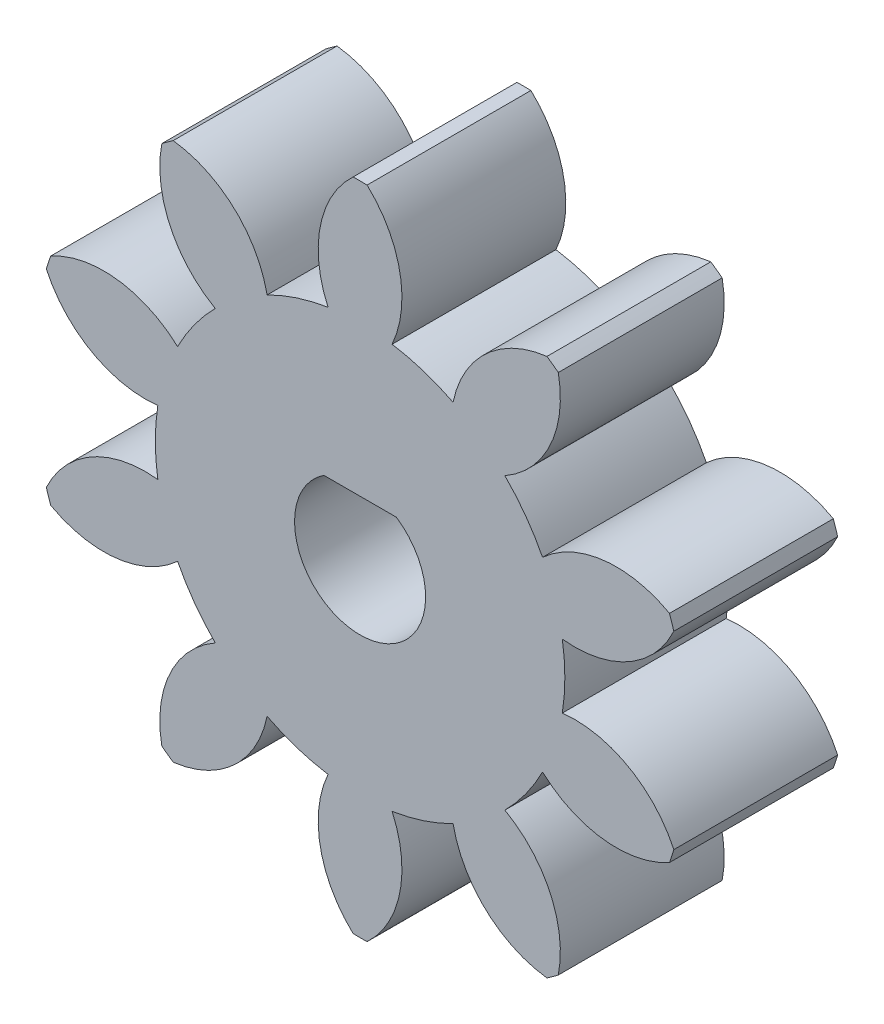
SolidWorks part; units mm, degrees
ref_plane "Front Plane" through (0, 0, 0) normal (0, 0, 1) x (1, 0, 0)
ref_plane "Top Plane" through (0, 0, 0) normal (0, 1, 0) x (1, 0, 0)
ref_plane "Right Plane" through (0, 0, 0) normal (1, 0, 0) x (0, 0, -1)
sketch "Sketch4" plane through (0, 0, 0) normal (0, 0, 1) x (1, 0, 0)
  point P0 (0, 12)
  arc B0 (11.3307, 3.9517) -> (6.6819, 3.404) centre (9.3858, 0.4563) ccw
  arc B1 (6.6819, 3.404) -> (5.3022, 5.303) centre (0, 0) ccw
  arc B2 (5.3022, 5.303) -> (7.2596, 9.555) centre (3.3343, 8.7855) ccw
  arc B3 (7.2596, 9.555) -> (6.844, 9.857) centre (0, 0) ccw
  arc B4 (6.844, 9.857) -> (3.405, 6.6814) centre (7.3251, 5.886) ccw
  arc B5 (3.405, 6.6814) -> (1.1725, 7.4068) centre (0, 0) ccw
  arc B6 (1.1725, 7.4068) -> (0.2569, 11.9973) centre (-2.4664, 9.0675) ccw
  arc B7 (0.2569, 11.9973) -> (-0.2569, 11.9973) centre (0, 0) ccw
  arc B8 (-0.2569, 11.9973) -> (-1.1725, 7.4068) centre (2.4664, 9.0675) ccw
  arc B9 (-1.1725, 7.4068) -> (-3.405, 6.6814) centre (0, 0) ccw
  arc B10 (-3.405, 6.6814) -> (-6.844, 9.857) centre (-7.3251, 5.886) ccw
  arc B11 (-6.844, 9.857) -> (-7.2596, 9.555) centre (0, 0) ccw
  arc B12 (-7.2596, 9.555) -> (-5.3022, 5.303) centre (-3.3343, 8.7855) ccw
  arc B13 (-5.3022, 5.303) -> (-6.6819, 3.404) centre (0, 0) ccw
  arc B14 (-6.6819, 3.404) -> (-11.3307, 3.9517) centre (-9.3858, 0.4563) ccw
  arc B15 (-11.3307, 3.9517) -> (-11.4894, 3.463) centre (0, 0) ccw
  arc B16 (-11.4894, 3.463) -> (-7.4066, 1.1737) centre (-7.8615, 5.1477) ccw
  arc B17 (-7.4066, 1.1737) -> (-7.4066, -1.1737) centre (0, 0) ccw
  arc B18 (-7.4066, -1.1737) -> (-11.4894, -3.463) centre (-7.8615, -5.1477) ccw
  arc B19 (-11.4894, -3.463) -> (-11.3307, -3.9517) centre (0, 0) ccw
  arc B20 (-11.3307, -3.9517) -> (-6.6819, -3.404) centre (-9.3858, -0.4563) ccw
  arc B21 (-6.6819, -3.404) -> (-5.3022, -5.303) centre (0, 0) ccw
  arc B22 (-5.3022, -5.303) -> (-7.2596, -9.555) centre (-3.3343, -8.7855) ccw
  arc B23 (-7.2596, -9.555) -> (-6.844, -9.857) centre (0, 0) ccw
  arc B24 (-6.844, -9.857) -> (-3.405, -6.6814) centre (-7.3251, -5.886) ccw
  arc B25 (-3.405, -6.6814) -> (-1.1725, -7.4068) centre (0, 0) ccw
  arc B26 (-1.1725, -7.4068) -> (-0.2569, -11.9973) centre (2.4664, -9.0675) ccw
  arc B27 (-0.2569, -11.9973) -> (0.2569, -11.9973) centre (0, 0) ccw
  arc B28 (0.2569, -11.9973) -> (1.1725, -7.4068) centre (-2.4664, -9.0675) ccw
  arc B29 (1.1725, -7.4068) -> (3.405, -6.6814) centre (0, 0) ccw
  arc B30 (3.405, -6.6814) -> (6.844, -9.857) centre (7.3251, -5.886) ccw
  arc B31 (6.844, -9.857) -> (7.2596, -9.555) centre (0, 0) ccw
  arc B32 (7.2596, -9.555) -> (5.3022, -5.303) centre (3.3343, -8.7855) ccw
  arc B33 (5.3022, -5.303) -> (6.6819, -3.404) centre (0, 0) ccw
  arc B34 (6.6819, -3.404) -> (11.3307, -3.9517) centre (9.3858, -0.4563) ccw
  arc B35 (11.3307, -3.9517) -> (11.4894, -3.463) centre (0, 0) ccw
  arc B36 (11.4894, -3.463) -> (7.4066, -1.1737) centre (7.8615, -5.1477) ccw
  arc B37 (7.4066, -1.1737) -> (7.4066, 1.1737) centre (0, 0) ccw
  arc B38 (7.4066, 1.1737) -> (11.4894, 3.463) centre (7.8615, 5.1477) ccw
  arc B39 (11.4894, 3.463) -> (11.3307, 3.9517) centre (0, 0) ccw
  circle B40 centre (0, 0) radius 2
sketch_block_instance "Block3-1"
sketch_block "Block3"
extrude "Boss-Extrude3" add sketch "Sketch4" along normal blind 6
sketch "Sketch6" plane through (0, 0, 6) normal (0, 0, 1) x (1, 0, 0)
  circle A0 centre (0, 0) radius 3.2769
extrude "Boss-Extrude4" add sketch "Sketch6" against normal up to surface (6 mm away) up to face at (0, 0, 0)
sketch "Sketch7" plane through (0, 0, 6) normal (0, 0, 1) x (1, 0, 0)
  line L0 (0, 0) -> (0, 2) construction
  line L1 (-1.3266, 2) -> (1.3266, 2)
  arc A0 (-1.3266, 2) -> (1.3266, 2) centre (0, 0) ccw
  dimension "D1" = 2
extrude "Cut-Extrude2" cut sketch "Sketch7" against normal up to surface (6 mm away) contours L1 A0 region at (0, -0.0896, 6) up to face at (0, 0, 0)
